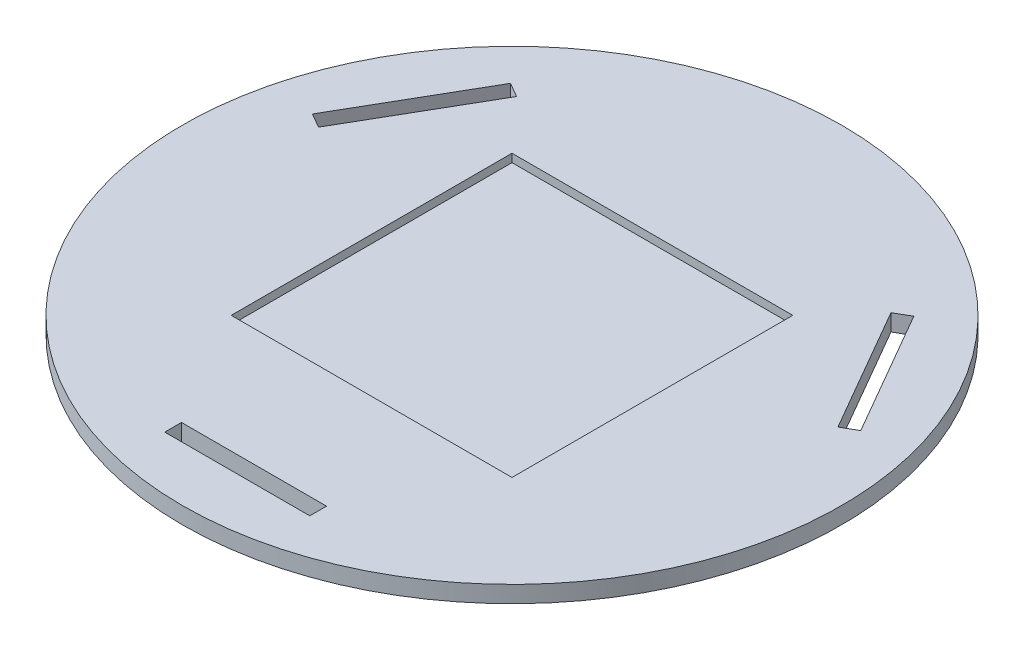
SolidWorks part; units mm, degrees
ref_plane "Front Plane" through (0, 0, 0) normal (0, 0, 1) x (1, 0, 0)
ref_plane "Top Plane" through (0, 0, 0) normal (0, 1, 0) x (1, 0, 0)
ref_plane "Right Plane" through (0, 0, 0) normal (1, 0, 0) x (0, 0, -1)
sketch "Sketch1" plane through (0, 0, 0) normal (0, 1, 0) x (1, 0, 0)
  circle A0 centre (0, 0) radius 125
  point P4 (0, 0)
  point P5 (0, 0)
  dimension "D1" = 250
extrude "Boss-Extrude1" add sketch "Sketch1" along normal blind 6.35
sketch "Sketch2" plane through (0, 0, 0) normal (0, -1, 0) x (1, 0, 0)
  line L0 (0, -202.0726) -> (-175, 101.0363) construction
  line L1 (-175, 101.0363) -> (175, 101.0363) construction
  line L2 (175, 101.0363) -> (0, -202.0726) construction
  line L3 (0, -202.0726) -> (0, 101.0363) construction
  line L4 (175, 101.0363) -> (-87.5, -50.5181) construction
  line L5 (-175, 101.0363) -> (87.5, -50.5181) construction
  line L6 (-175, -101.0363) -> (175, -101.0363) construction
  line L7 (175, -101.0363) -> (0, 202.0726) construction
  line L8 (0, 202.0726) -> (-175, -101.0363) construction
  line L9 (0, 202.0726) -> (0, -101.0363) construction
  line L10 (-175, -101.0363) -> (87.5, 50.5181) construction
  line L11 (175, -101.0363) -> (-87.5, 50.5181) construction
  point P0 (0, 0)
  point P4 (0, 0)
  point P12 (0, 0)
  dimension "D1" = 350
  dimension "D2" = 350
ref_axis "Axis1" through (0, 6.35, 0) along (0, -1, 0)
sketch "Sketch3" plane through (0, 6.35, 0) normal (0, 1, 0) x (1, 0, 0)
  line L0 (0, 202.0726) -> (-175, -101.0363) construction
  line L1 (-98.5004, 25.1149) -> (-103.9996, 28.2899)
  line L2 (-98.5004, 25.1149) -> (-71.0004, 72.7463)
  line L3 (-71.0004, 72.7463) -> (-76.4996, 75.9213)
  line L4 (-103.9996, 28.2899) -> (-76.4996, 75.9213)
  line L5 (175, -101.0363) -> (-87.5, 50.5181) construction
  line L6 (71.0004, 72.7463) -> (98.5004, 25.1149)
  line L7 (98.5004, 25.1149) -> (103.9996, 28.2899)
  line L8 (103.9996, 28.2899) -> (76.4996, 75.9213)
  line L9 (76.4996, 75.9213) -> (71.0004, 72.7463)
  line L10 (175, -101.0363) -> (0, 202.0726) construction
  line L11 (175, 101.0363) -> (-87.5, -50.5181) construction
  line L12 (0, 202.0726) -> (0, -101.0363) construction
  line L13 (-27.5, -97.8613) -> (27.5, -97.8613)
  line L14 (-27.5, -97.8613) -> (-27.5, -104.2113)
  line L15 (-27.5, -104.2113) -> (27.5, -104.2113)
  line L16 (27.5, -97.8613) -> (27.5, -104.2113)
  line L17 (-175, -101.0363) -> (175, -101.0363) construction
  point P6 (-90.2496, 52.1056)
  point P11 (-73.75, 74.3338)
  point P18 (90.2496, 52.1056)
  point P21 (73.75, 74.3338)
  point P26 (0, -97.8613)
  point P29 (-27.5, -101.0363)
  dimension "D1" = 6.35
  dimension "D2" = 55
  dimension "D3" = 55
  dimension "D4" = 6.35
  dimension "D5" = 55
  dimension "D6" = 6.35
extrude "Cut-Extrude1" cut sketch "Sketch3" against normal through all
sketch "Sketch4" plane through (0, 6.35, 0) normal (0, 1, 0) x (1, 0, 0)
  line L1 (-53.25, 53.25) -> (53.25, 53.25)
  line L2 (-53.25, 53.25) -> (-53.25, -53.25)
  line L3 (-53.25, -53.25) -> (53.25, -53.25)
  line L4 (53.25, 53.25) -> (53.25, -53.25)
  point P4 (0, 53.25)
  point P6 (-53.25, 0)
  dimension "D1" = 106.5
sketch "Sketch5" plane through (0, 6.35, 0) normal (0, 1, 0) x (1, 0, 0)
  line L1 (-53.25, 53.25) -> (53.25, 53.25)
  line L2 (-53.25, 53.25) -> (-53.25, -53.25)
  line L3 (-53.25, -53.25) -> (53.25, -53.25)
  line L4 (53.25, 53.25) -> (53.25, -53.25)
  point P4 (0, 53.25)
  point P6 (-53.25, 0)
  dimension "D1" = 106.5
extrude "Cut-Extrude2" cut sketch "Sketch4" against normal blind 3.1
sketch "Sketch6" plane through (0, 0, 0) normal (0, -1, 0) x (1, 0, 0)
  point P0 (0, 0)
